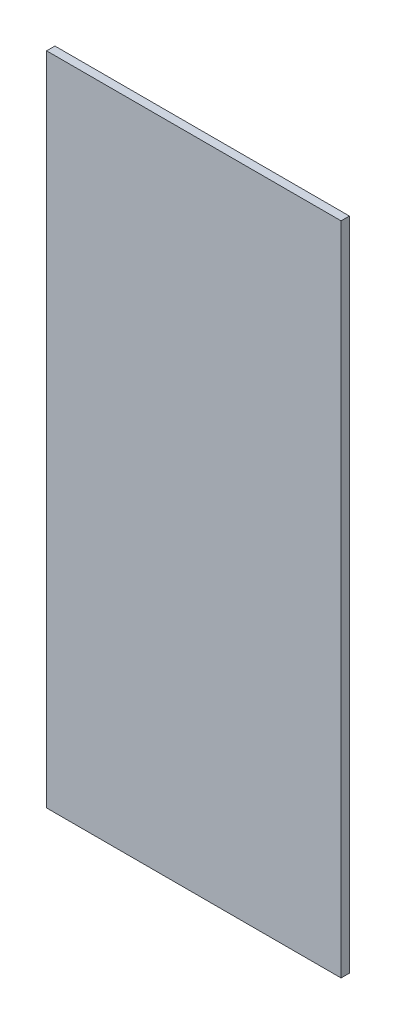
SolidWorks part; units mm, degrees
ref_plane "Front Plane" through (0, 0, 0) normal (0, 0, 1) x (1, 0, 0)
ref_plane "Top Plane" through (0, 0, 0) normal (0, 1, 0) x (1, 0, 0)
ref_plane "Right Plane" through (0, 0, 0) normal (1, 0, 0) x (0, 0, -1)
sketch "Sketch1" plane through (0, 0, 0) normal (0, 0, 1) x (1, 0, 0)
  line L1 (-90.5335, 303.6022) -> (134.0132, 303.6022)
  line L2 (-90.5335, 303.6022) -> (-90.5335, -196.3978)
  line L3 (-90.5335, -196.3978) -> (134.0132, -196.3978)
  line L4 (134.0132, 303.6022) -> (134.0132, -196.3978)
  dimension "D1" = 500
extrude "Boss-Extrude1" add sketch "Sketch1" along normal blind 6.35
sketch "Sketch2" plane through (0, 0, 0) normal (0, 0, -1) x (-1, 0, 0)
  line L0 (-21.7398, -196.3978) -> (-21.7398, 303.6022) construction
  line L1 (90.5335, -196.3978) -> (-134.0132, -196.3978) construction
  line L2 (-134.0132, 303.6022) -> (90.5335, 303.6022) construction
  line L3 (-36.7398, 3.6022) -> (-6.7398, 3.6022) construction
  line L4 (-36.7398, 103.6022) -> (-6.7398, 103.6022) construction
  line L5 (-36.7398, 203.6022) -> (-6.7398, 203.6022) construction
  point P8 (-21.7398, 3.6022)
  point P11 (-21.7398, 103.6022)
  point P14 (0, 0)
  point P15 (0, 0)
  point P16 (0, 0)
  dimension "D1" = 30
  dimension "D2" = 30
  dimension "D3" = 100
  dimension "D4" = 100
  dimension "D5" = 200
